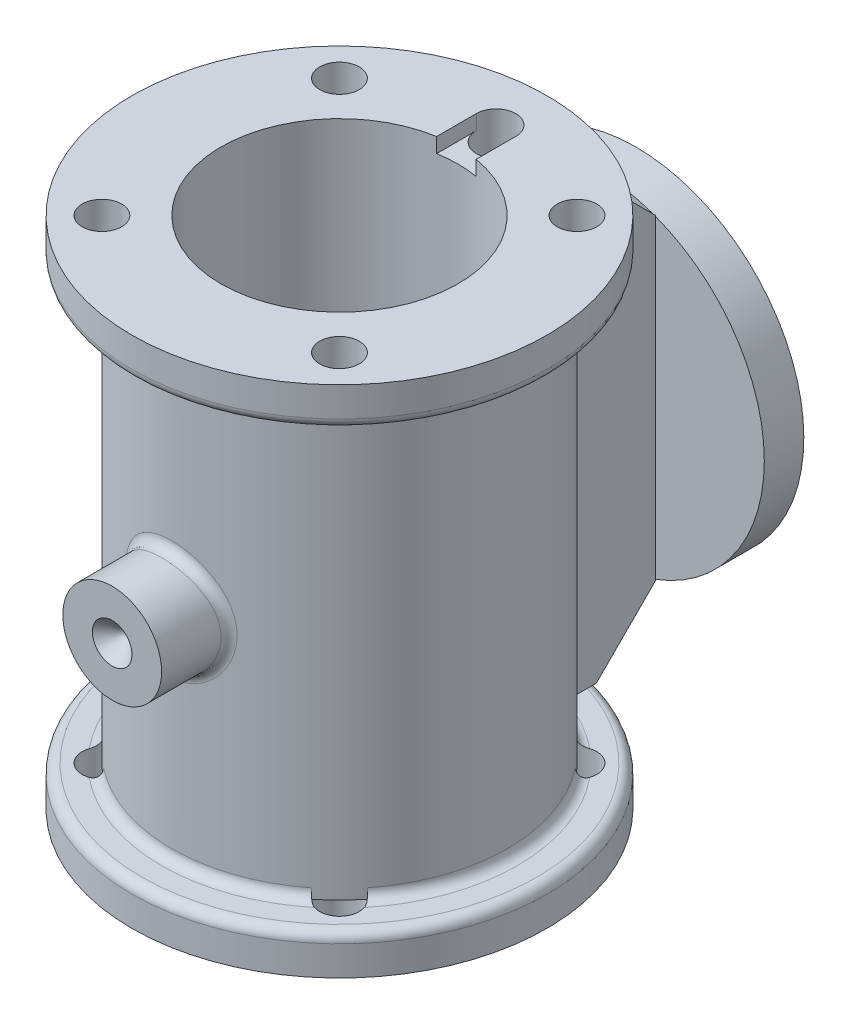
SolidWorks part; units mm, degrees
note: The reader was unsure of these and kept them because the rebuilt part matched: shared geometry of "Sketch1<2>", "Sketch6<2>", "Sketch6<3>".
ref_plane "Front Plane" through (0, 0, 0) normal (0, 0, 1) x (1, 0, 0)
ref_plane "Top Plane" through (0, 0, 0) normal (0, 1, 0) x (1, 0, 0)
ref_plane "Right Plane" through (0, 0, 0) normal (1, 0, 0) x (0, 0, -1)
sketch "Sketch1" plane through (0, 0, 0) normal (0, 1, 0) x (1, 0, 0)
  line L0 (0, 0) -> (0, 17) construction
  line L1 (0, 0) -> (-12.0208, 12.0208) construction
  circle A0 centre (0, 0) radius 21
  circle A1 centre (0, 0) radius 12
  circle A2 centre (0, 0) radius 17 construction
  circle A3 centre (-12.0208, 12.0208) radius 2
  circle A4 centre (12.0208, 12.0208) radius 2
  circle A5 centre (12.0208, -12.0208) radius 2
  circle A6 centre (-12.0208, -12.0208) radius 2
  point P17 (0, 0)
  dimension "D1" = 45
  dimension "D2" = 4
  dimension "D3" = 42
  dimension "D4" = 34
  dimension "D5" = 24
extrude "Boss-Extrude1" add sketch "Sketch1" along normal blind 4
cosmetic thread "Cosmetic Thread3" parameters "D1"=4, "D2"=5
cosmetic thread "Cosmetic Thread4" parameters "D1"=4, "D2"=5
cosmetic thread "Cosmetic Thread5" parameters "D1"=4, "D2"=5
cosmetic thread "Cosmetic Thread6" parameters "D1"=4, "D2"=5
extrude "Boss-Extrude2" add sketch "Sketch1<2>" against normal blind 4 from offset 44 separate body offset against normal yes
sketch "Sketch1<2>" plane through (0, 0, 0) normal (0, 1, 0) x (1, 0, 0) same geometry as "Sketch1"
cosmetic thread "Cosmetic Thread8" parameters "D1"=4, "D2"=5
cosmetic thread "Cosmetic Thread9" parameters "D1"=4, "D2"=5
cosmetic thread "Cosmetic Thread10" parameters "D1"=4, "D2"=5
cosmetic thread "Cosmetic Thread11" parameters "D1"=4, "D2"=5
sketch "Sketch2" plane through (0, 0, 0) normal (0, 1, 0) x (1, 0, 0)
  circle A0 centre (0, 0) radius 17
extrude "Boss-Extrude3" add sketch "Sketch2" against normal blind 44
sketch "Sketch3" plane through (0, -44, 0) normal (0, -1, 0) x (1, 0, 0)
  circle A1 centre (0, 0) radius 12
  circle A2 centre (0, 0) radius 12
  dimension "D1" = 0
extrude "Cut-Extrude1" cut sketch "Sketch3" against normal blind 48
ref_plane "Plane2" through (0, 0, 23) normal (0, 0, 1) x (1, 0, 0)
sketch "Sketch10" plane through (0, 0, 23) normal (0, 0, 1) x (1, 0, 0)
  line L0 (12, 4) -> (-12, 4) construction
  circle A0 centre (0, -22) radius 5
  dimension "D1" = 10
  dimension "D2" = 26
extrude "Boss-Extrude8" add sketch "Sketch10" against normal up to surface (12.0913 mm away)
fillet "Fillet2" radius 1 11 edges at (0, 0, 21) (0, 0, 17) (-17, 0, 0) (0, 0, -17) (17, 0, 0) (17, -44, 0) (0, -44, -17) (-17, -44, 0) (0, -44, 17) (0, -44, 21) (-0.914, -17.0843, 16.9754)
ref_plane "Plane1" through (0, 0, -16) normal (0, 0, 1) x (1, 0, 0)
sketch "Sketch5" plane through (0, 0, -16) normal (0, 0, 1) x (1, 0, 0)
  line L1 (6, -44) -> (-6, -44)
  line L2 (6, -44) -> (6, 0)
  line L3 (6, 0) -> (-6, 0)
  line L4 (-6, -44) -> (-6, 0)
  point P0 (0, -22)
extrude "Boss-Extrude5" add sketch "Sketch5" against normal blind 10
chamfer "Chamfer1" distance 6 angle 45 2 edges at (0, -44, -26) (0, 0, -26)
sketch "Sketch6" plane through (0, 0, -26) normal (0, 0, -1) x (-1, 0, 0)
  line L0 (-21, -48) -> (21, -48) construction
  circle A0 centre (0, -22) radius 17
  circle A1 centre (0, -22) radius 2
  circle A2 centre (0, -10) radius 2
  circle A3 centre (0, -34) radius 2
  point P7 (0, -22)
  dimension "D1" = 26
extrude "Boss-Extrude6" add sketch "Sketch6" along normal blind 4
cosmetic thread "Cosmetic Thread1" parameters "D1"=4, "D2"=5
cosmetic thread "Cosmetic Thread2" parameters "D1"=4, "D2"=5
extrude "Boss-Extrude7" add sketch "Sketch6<2>" along normal blind 12 contours A1
sketch "Sketch6<2>" plane through (0, 0, -26) normal (0, 0, -1) x (-1, 0, 0) same geometry as "Sketch6"
extrude "Cut-Extrude2" cut sketch "Sketch6<3>" against normal blind 12 contours A2 | A3
sketch "Sketch6<3>" plane through (0, 0, -26) normal (0, 0, -1) x (-1, 0, 0) same geometry as "Sketch6"
sketch "Sketch7" plane through (0, 4, 0) normal (0, 1, 0) x (1, 0, 0)
  circle A0 centre (0, 15.8471) radius 2
extrude "Cut-Extrude3" cut sketch "Sketch7" against normal blind 16
cosmetic thread "Cosmetic Thread7" parameters "D1"=4, "D2"=5
sketch "Sketch8" plane through (0, 4, 0) normal (0, 1, 0) x (1, 0, 0)
  line L0 (-2, 15.8471) -> (-2, 9.3337)
  line L1 (-2, 9.3337) -> (2, 9.3337)
  line L2 (2, 9.3337) -> (2, 15.8471)
  arc A0 (2, 15.8471) -> (-2, 15.8471) centre (0, 15.8471) ccw
extrude "Cut-Extrude4" cut sketch "Sketch8" against normal blind 1.5
sketch "Sketch9" plane through (0, -48, 0) normal (0, -1, 0) x (1, 0, 0)
  line L0 (-2, -15.0173) -> (-2, -9.9146)
  line L1 (-2, -9.9146) -> (2, -9.9146)
  line L2 (2, -9.9146) -> (2, -15.0173)
  arc A0 (-2, -15.0173) -> (2, -15.0173) centre (0, -15.0173) ccw
extrude "Cut-Extrude5" cut sketch "Sketch9" against normal blind 1.5
sketch "Sketch12" plane through (0, 0, 0) normal (1, 0, 0) x (0, 0, -1)
  line L0 (-23, -22) -> (-21, -22) construction
  line L1 (-23, -17) -> (-23, -27) construction
  line L2 (-21, -22) -> (-24.1304, -18.8696)
  line L6 (-24.1304, -18.8696) -> (-24.1304, -22)
  line L7 (-24.1304, -18.8696) -> (-24.1304, -22)
  line L8 (-21, -22) -> (-24.1304, -22)
  dimension "D1" = 45
revolve "Cut-Revolve1" cut sketch "Sketch12" angle 360 about L0
